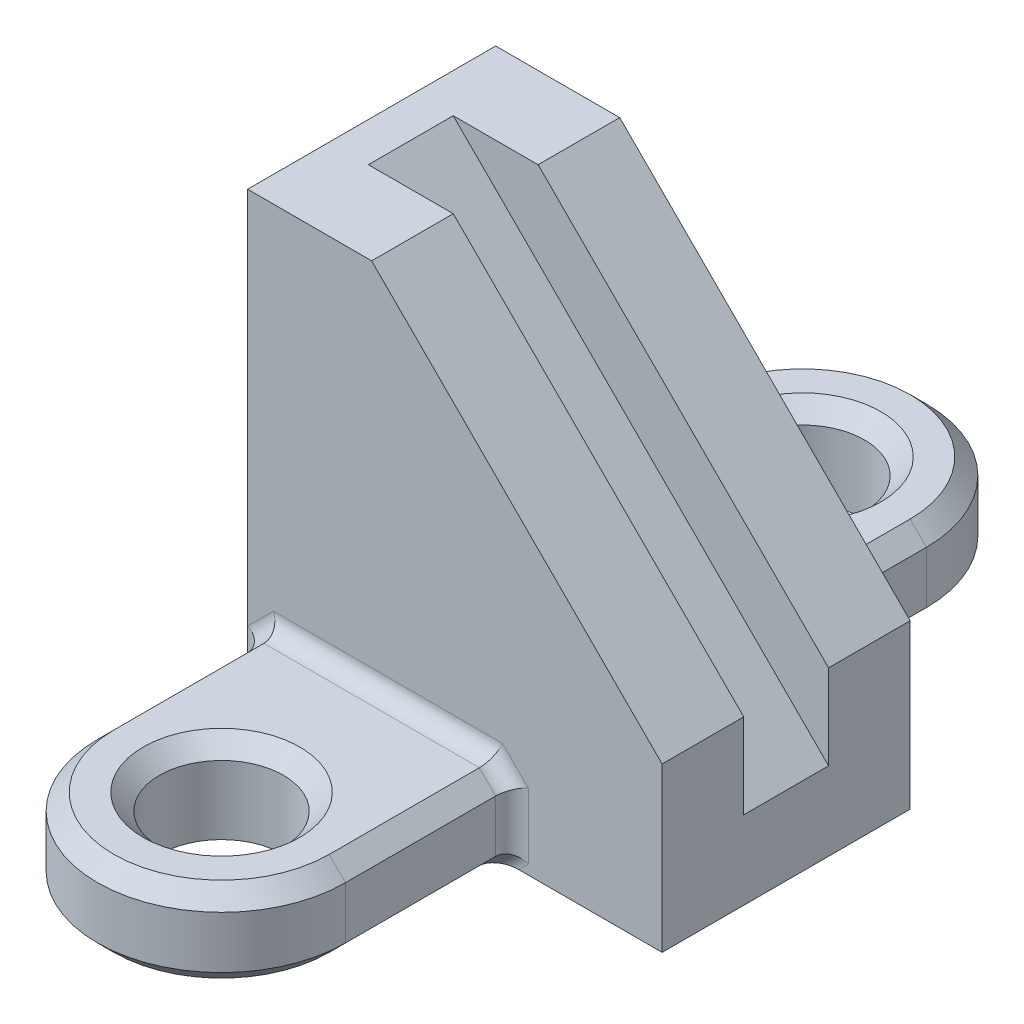
SolidWorks part; units mm, degrees
material "Alloy Steel"
ref_plane "Front Plane" through (0, 0, 0) normal (0, 0, 1) x (1, 0, 0)
ref_plane "Top Plane" through (0, 0, 0) normal (0, 1, 0) x (1, 0, 0)
ref_plane "Right Plane" through (0, 0, 0) normal (1, 0, 0) x (0, 0, -1)
sketch "Sketch1" plane through (0, 0, 0) normal (0, 0, 1) x (1, 0, 0)
  line L0 (0, 139) -> (0, 0)
  line L1 (0, 0) -> (127, 0)
  line L2 (127, 0) -> (127, 50)
  line L3 (127, 50) -> (38, 139)
  line L4 (38, 139) -> (0, 139)
  point P6 (0, 0)
  point P7 (0, 0)
  dimension "D1" = 50
  dimension "D2" = 135
  dimension "D3" = 38
  dimension "D4" = 127
extrude "Boss-Extrude1" add sketch "Sketch1" along normal mid plane 76
sketch "Sketch2" plane through (0, 139, 0) normal (0, 1, 0) x (1, 0, 0)
  line L0 (38, -38) -> (38, 38) construction
  line L1 (38, 13) -> (12, 13)
  line L2 (38, 13) -> (38, -13)
  line L3 (38, -13) -> (12, -13)
  line L4 (12, 13) -> (12, -13)
  point P6 (38, -13.6055)
  point P8 (12, 0)
  dimension "D1" = 26
  dimension "D2" = 26
extrude "Cut-Extrude1" cut sketch "Sketch2" along direction (-0.7071, 0.7071, 0) on the side against the normal up to surface (125.865 mm away) up to face at (127, 25, 0)
sketch "Sketch3" plane through (0, 0, 0) normal (0, -1, 0) x (1, 0, 0)
  line L0 (5, 38) -> (5, 89)
  line L1 (81, 89) -> (81, 38)
  line L2 (0, 38) -> (127, 38) construction
  line L3 (81, 38) -> (5, 38)
  line L4 (0, 38) -> (0, -38) construction
  arc A0 (5, 89) -> (81, 89) centre (43, 89) cw
  point P5 (0, 0)
  dimension "D1" = 76
  dimension "D2" = 51
  dimension "D3" = 5
extrude "Boss-Extrude2" add sketch "Sketch3" against normal blind 26
chamfer "Chamfer2" distance 5 angle 45 6 edges at (5, 0, 63.5) (43, 0, 127) (81, 0, 63.5) (5, 26, 63.5) (43, 26, 127) (81, 26, 63.5)
fillet "Fillet4" radius 5 7 edges at (7.5, 2.5, 38) (5, 13, 38) (7.5, 23.5, 38) (78.5, 2.5, 38) (81, 13, 38) (78.5, 23.5, 38) (43, 26, 38)
sketch "Sketch4" plane through (0, 26, 0) normal (0, 1, 0) x (1, 0, 0)
  circle A0 centre (43, -89) radius 19
  arc A1 (10, -89) -> (76, -89) centre (43, -89) ccw construction
  point P2 (44.677, -89)
  dimension "D1" = 38
extrude "Cut-Extrude2" cut sketch "Sketch4" against normal blind 26 contours A0
chamfer "Chamfer3" distance 5 angle 45 1 edges at (43, 26, 108)
mirror "Mirror1" about plane through (0, 0, 0) normal (0, 0, 1) of "Chamfer3", "Cut-Extrude2", "Boss-Extrude2"
chamfer "Chamfer4" distance 5 angle 45 6 edges at (5, 0, -63.5) (43, 0, -127) (81, 0, -63.5) (5, 26, -63.5) (43, 26, -127) (81, 26, -63.5)
fillet "Fillet5" radius 5 7 edges at (78.5, 2.5, -38) (7.5, 2.5, -38) (5, 13, -38) (7.5, 23.5, -38) (43, 26, -38) (78.5, 23.5, -38) (81, 13, -38)
